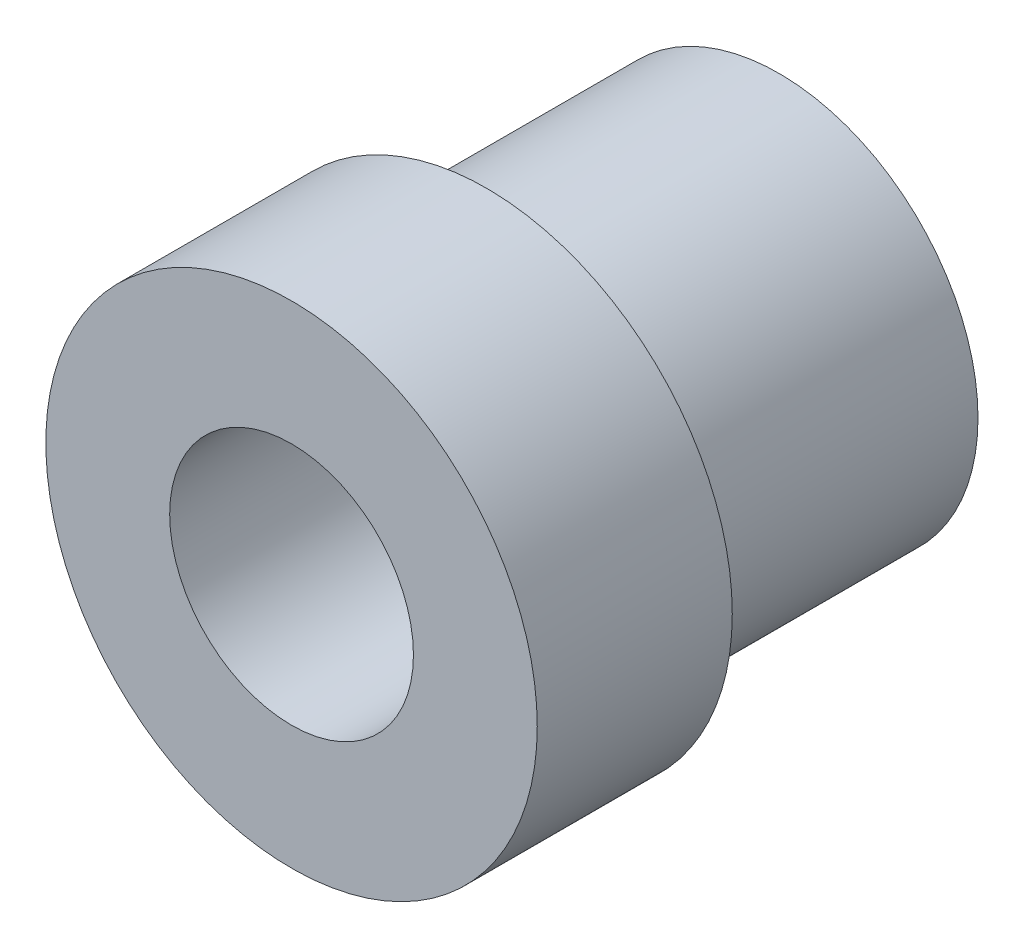
SolidWorks part; units mm, degrees
ref_plane "Front Plane" through (0, 0, 0) normal (0, 0, 1) x (1, 0, 0)
ref_plane "Top Plane" through (0, 0, 0) normal (0, 1, 0) x (1, 0, 0)
ref_plane "Right Plane" through (0, 0, 0) normal (1, 0, 0) x (0, 0, -1)
sketch "Sketch1" plane through (0, 0, 0) normal (0, 0, 1) x (1, 0, 0)
  circle A0 centre (0, 0) radius 6.477
  circle A1 centre (0, 0) radius 8.001
  circle A2 centre (0, 0) radius 3.9688
  dimension "D1" = 16.002
  dimension "D2" = 12.954
  dimension "D3" = 7.9375
extrude "Outer" add sketch "Sketch1" along normal blind 6.35 contours A1 A0 | A0 A2 region at (-6.2938, 0, 0) region at (-7.7747, 0, 0)
extrude "Boss-Extrude2" add sketch "Sketch1<3>" against normal blind 9.525 contours A0 A2 region at (-6.2938, 0, 0)
sketch "Sketch1<3>" plane through (0, 0, 0) normal (0, 0, 1) x (1, 0, 0) same geometry as "Sketch1"
equation "\"threaded_insert_hole_diameter\"= 5 / 16"
equation "\"threaded_insert_smaller_diameter\"= \"threaded_insert_bigger_diameter\" - .12"
equation "\"threaded_insert_bigger_diameter\" = .63"
equation "\"D1@Sketch1\"=\"threaded_insert_bigger_diameter\""
equation "\"D2@Sketch1\"=\"threaded_insert_smaller_diameter\""
equation "\"D3@Sketch1\"=\"threaded_insert_hole_diameter\""
equation "\"threaded_insert_inner_length\" = .375"
equation "\"threaded_insert_outer_length\" = .25"
equation "\"D1@Outer\" = \"threaded_insert_outer_length\""
equation "\"D1@Boss-Extrude2\"=\"threaded_insert_inner_length\""
